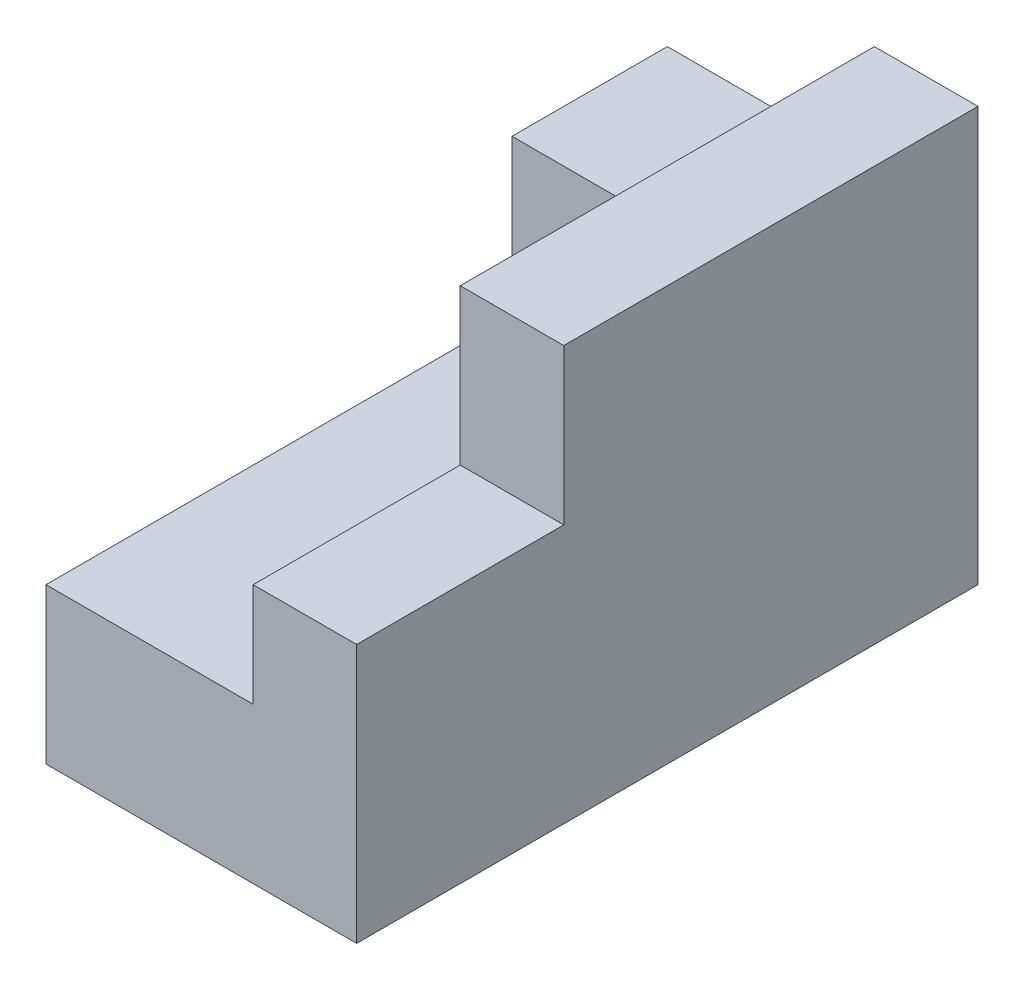
SolidWorks part; units mm, degrees
ref_plane "Front Plane" through (0, 0, 0) normal (0, 0, 1) x (1, 0, 0)
ref_plane "Top Plane" through (0, 0, 0) normal (0, 1, 0) x (1, 0, 0)
ref_plane "Right Plane" through (0, 0, 0) normal (1, 0, 0) x (0, 0, -1)
sketch "Sketch1" plane through (0, 0, 0) normal (0, 0, 1) x (1, 0, 0)
  line L0 (-30, 30) -> (-10, 30)
  line L1 (-10, 30) -> (-10, 40)
  line L2 (-10, 40) -> (0, 40)
  line L3 (0, 40) -> (0, 0)
  line L4 (0, 0) -> (-30, 0)
  line L5 (-30, 0) -> (-30, 30)
  line L6 (-30, 15) -> (-10, 15)
  line L7 (-10, 15) -> (-10, 30)
  line L8 (-10, 25) -> (0, 25)
  point P10 (0, 0)
  point P11 (0, 0)
  point P12 (-34.0109, 56.3793)
  point P13 (0, 0)
  dimension "D1" = 30
  dimension "D2" = 25
  dimension "D3" = 15
  dimension "D4" = 30
  dimension "D5" = 10
  dimension "D6" = 40
extrude "Boss-Extrude1" add sketch "Sketch1" along normal blind 15 contours L6 L7 L0 L5 region at (-20, 22.5, 0)
extrude "Boss-Extrude2" add sketch "Sketch1<3>" along normal blind 60 contours L8 L7 L6 L5 L4 L3 region at (-13.1818, 9.7727, 0)
sketch "Sketch1<3>" plane through (0, 0, 0) normal (0, 0, 1) x (1, 0, 0) same geometry as "Sketch1"
extrude "Boss-Extrude3" add sketch "Sketch1<4>" along normal blind 40 contours L7 L8 L3 L2 L1 region at (-5, 32.5, 0)
sketch "Sketch1<4>" plane through (0, 0, 0) normal (0, 0, 1) x (1, 0, 0) same geometry as "Sketch1"
